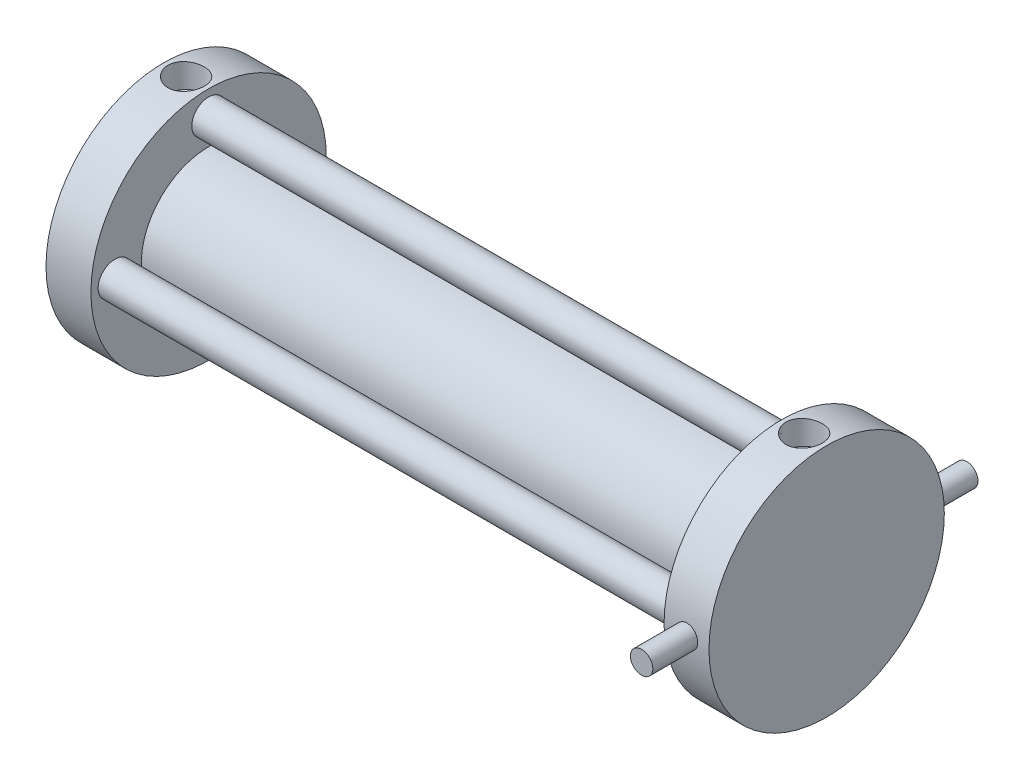
SolidWorks part; units mm, degrees
ref_plane "Front Plane" through (0, 0, 0) normal (0, 0, 1) x (1, 0, 0)
ref_plane "Top Plane" through (0, 0, 0) normal (0, 1, 0) x (1, 0, 0)
ref_plane "Right Plane" through (0, 0, 0) normal (1, 0, 0) x (0, 0, -1)
sketch "Sketch1" plane through (0, 0, 0) normal (1, 0, 0) x (0, 0, -1)
  circle A0 centre (0, 0) radius 33.274
  dimension "D1" = 66.548
extrude "Boss-Extrude1" add sketch "Sketch1" along normal blind 12.7
sketch "Sketch2" plane through (12.7, 0, 0) normal (1, 0, 0) x (0, 0, -1)
  circle A0 centre (0, 0) radius 19.05
  dimension "D1" = 38.1
extrude "Boss-Extrude2" add sketch "Sketch2" along normal blind 162.052
sketch "Sketch3" plane through (174.752, 0, 0) normal (1, 0, 0) x (0, 0, -1)
  circle A0 centre (0, 0) radius 33.274
  dimension "D1" = 66.548
extrude "Boss-Extrude3" add sketch "Sketch3" along normal blind 12.7
sketch "Sketch4" plane through (187.452, 0, 0) normal (1, 0, 0) x (0, 0, -1)
  line L0 (0, 0) -> (33.274, 0) construction
  circle A0 centre (26.4795, 0) radius 4.7625
  circle A2 centre (0, 0) radius 33.274 construction
  circle A3 centre (0, -26.4795) radius 4.7625
  circle A4 centre (-26.4795, 0) radius 4.7625
  circle A5 centre (0, 26.4795) radius 4.7625
  point P8 (31.242, 0)
  point P18 (0, 0)
  dimension "D1" = 9.525
  dimension "D2" = 2.032
  dimension "D3" = 4
extrude "Boss-Extrude4" add sketch "Sketch4" against normal up to surface (174.752 mm away) up to face at (12.7, 0, -19.05)
ref_plane "Plane1" through (0, 0, -33.274) normal (0, 0, -1) x (-1, 0, 0)
sketch "Sketch5" plane through (0, 0, -33.274) normal (0, 0, -1) x (-1, 0, 0)
  line L0 (-187.452, 33.274) -> (-187.452, -33.274) construction
  circle A0 centre (-181.102, 0) radius 3.175
  dimension "D1" = 6.35
  dimension "D2" = 6.35
extrude "Boss-Extrude5" add sketch "Sketch5" along normal blind 12.7 and the other way up to surface other way up to face at (187.452, 0, -33.274)
ref_plane "Plane2" through (0, 0, 33.274) normal (0, 0, 1) x (1, 0, 0)
sketch "Sketch6" plane through (0, 0, 33.274) normal (0, 0, 1) x (1, 0, 0)
  line L0 (174.752, 4.7625) -> (174.752, -4.7625) construction
  circle A0 centre (181.102, 0) radius 3.175
  dimension "D1" = 6.35
  dimension "D2" = 6.35
extrude "Boss-Extrude6" add sketch "Sketch6" against normal up to surface and the other way blind 12.7 up to face at (187.452, 0, -33.274)
ref_plane "Plane3" through (0, 33.274, 0) normal (0, 1, 0) x (1, 0, 0)
hole_wizard "1/8 NPT Tapped Hole1" positions "Sketch7" profile "Sketch8" size "1/8" standard "ANSI Inch"
sketch "Sketch7" plane through (0, 33.274, 0) normal (0, 1, 0) x (1, 0, 0)
  line L0 (187.452, -33.274) -> (187.452, 33.274) construction
  point P0 (181.102, 0)
  point P2 (6.35, 0)
  dimension "D1" = 6.35
  dimension "D2" = 6.35
sketch "Sketch8" plane through (181.102, 33.274, 0) normal (1, 0, 0) x (0, 0, 1)
  line L0 (0, 0) -> (0, 14.2175)
  line L1 (4.2164, 11.684) -> (0, 14.2175)
  line L2 (-4.2164, 11.684) -> (0, 14.2175) construction
  line L3 (4.2164, 11.684) -> (4.2164, 6.858)
  line L4 (4.2164, 6.858) -> (4.9362, 6.858)
  line L5 (4.9362, 6.858) -> (5.1415, 0)
  line L6 (-4.9362, 6.858) -> (-5.1415, 0) construction
  line L7 (5.1415, 0) -> (0, 0)
  line L8 (0, -6.35) -> (0, 107.95) construction
  line L11 (-4.2164, 6.858) -> (-4.9362, 6.858) construction
  dimension "Tap Drill Dia." = 8.4328
  dimension "Tap Drill Depth" = 11.684
  dimension "Thread Dia." = 10.283
  dimension "Thread Angle" = 3.43
  dimension "Thread Depth" = 6.858
  dimension "Drill Angle" = 118
